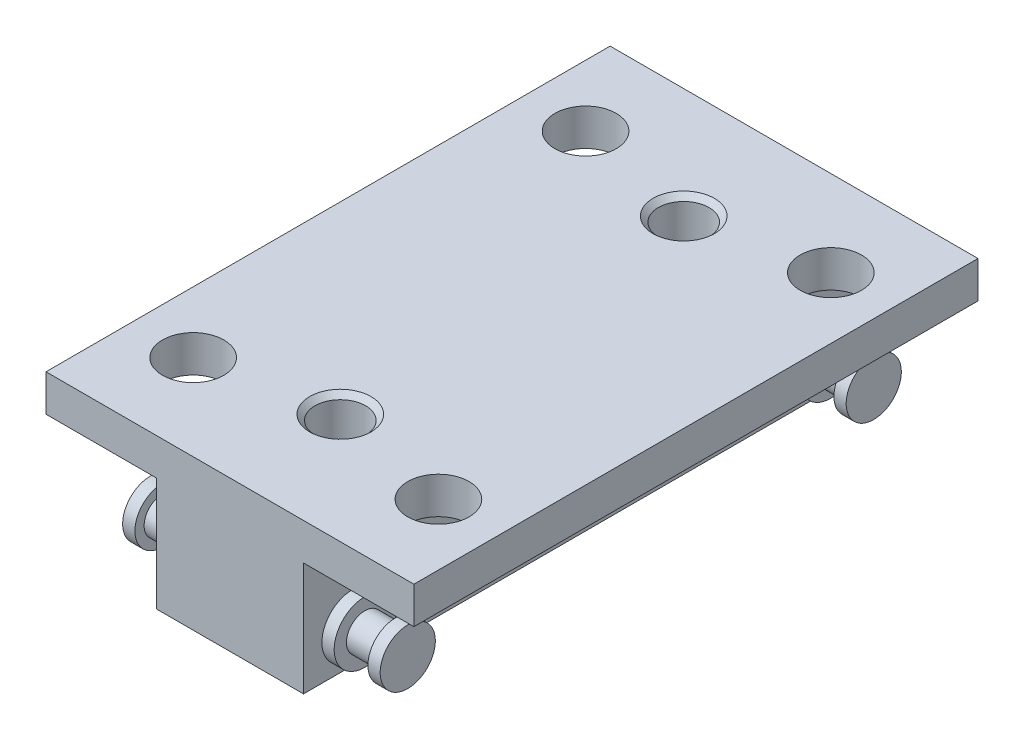
SolidWorks part; units mm, degrees
ref_plane "Front Plane" through (0, 0, 0) normal (0, 0, 1) x (1, 0, 0)
ref_plane "Top Plane" through (0, 0, 0) normal (0, 1, 0) x (1, 0, 0)
ref_plane "Right Plane" through (0, 0, 0) normal (1, 0, 0) x (0, 0, -1)
ref_plane "Plane1" through (0, 0, 0) normal (0, 0, 1) x (1, 0, 0)
sketch "Sketch1" plane through (0, 0, 0) normal (0, 0, 1) x (1, 0, 0)
  line L0 (-15, 6.25) -> (-15, 3.25)
  line L1 (-15, 3.25) -> (-6, 3.25)
  line L2 (-6, 3.25) -> (-6, -6)
  line L3 (-6, -6) -> (6, -6)
  line L4 (6, -6) -> (6, 3.25)
  line L5 (6, 3.25) -> (15, 3.25)
  line L6 (15, 3.25) -> (15, 6.25)
  line L7 (15, 6.25) -> (-15, 6.25)
extrude "Boss-Extrude1" add sketch "Sketch1" against normal blind 23 and the other way blind 23
ref_plane "Plane2" through (0, 0, 19) normal (0, 0, 1) x (1, 0, 0)
sketch "Sketch2" plane through (0, 0, 19) normal (0, 0, 1) x (1, 0, 0)
  line L0 (10.5, -3.125) -> (10.5, -5.375)
  line L1 (10.5, -5.375) -> (9.5, -5.375)
  line L2 (9.5, -5.375) -> (9.5, -4.625)
  line L3 (9.5, -4.625) -> (7, -4.625)
  line L4 (7, -4.625) -> (7, -5.625)
  line L5 (7, -5.625) -> (6, -5.625)
  line L6 (6, -5.625) -> (6, -4.625)
  line L7 (6, -4.625) -> (-6, -4.625)
  line L8 (-6, -4.625) -> (-6, -5.625)
  line L9 (-6, -5.625) -> (-7, -5.625)
  line L10 (-7, -5.625) -> (-7, -4.625)
  line L11 (-7, -4.625) -> (-9.5, -4.625)
  line L12 (-9.5, -4.625) -> (-9.5, -5.375)
  line L13 (-9.5, -5.375) -> (-10.5, -5.375)
  line L14 (-10.5, -5.375) -> (-10.5, -3.125)
  line L15 (-10.5, -3.125) -> (10.5, -3.125)
  line L16 (-10.5, -3.125) -> (10.5, -3.125) construction
revolve "Revolve1" add sketch "Sketch2" angle 360 about L16 reverse direction yes
ref_plane "Plane3" through (0, 0, -19) normal (0, 0, 1) x (1, 0, 0)
sketch "Sketch3" plane through (0, 0, -19) normal (0, 0, 1) x (1, 0, 0)
  line L0 (10.5, -3.125) -> (10.5, -5.375)
  line L1 (10.5, -5.375) -> (9.5, -5.375)
  line L2 (9.5, -5.375) -> (9.5, -4.625)
  line L3 (9.5, -4.625) -> (7, -4.625)
  line L4 (7, -4.625) -> (7, -5.625)
  line L5 (7, -5.625) -> (6, -5.625)
  line L6 (6, -5.625) -> (6, -4.625)
  line L7 (6, -4.625) -> (-6, -4.625)
  line L8 (-6, -4.625) -> (-6, -5.625)
  line L9 (-6, -5.625) -> (-7, -5.625)
  line L10 (-7, -5.625) -> (-7, -4.625)
  line L11 (-7, -4.625) -> (-9.5, -4.625)
  line L12 (-9.5, -4.625) -> (-9.5, -5.375)
  line L13 (-9.5, -5.375) -> (-10.5, -5.375)
  line L14 (-10.5, -5.375) -> (-10.5, -3.125)
  line L15 (-10.5, -3.125) -> (10.5, -3.125)
  line L16 (-10.5, -3.125) -> (10.5, -3.125) construction
revolve "Revolve2" add sketch "Sketch3" angle 360 about L16 reverse direction yes
ref_plane "Plane4" through (0, 0, 0) normal (1, 0, 0) x (0, 0, -1)
sketch "Sketch4" plane through (0, 0, 0) normal (1, 0, 0) x (0, 0, -1)
  line L0 (-14, 6.25) -> (-11.5, 6.25)
  line L1 (-11.5, 6.25) -> (-11.933, 5.817)
  line L2 (-11.933, 5.817) -> (-11.933, -5.567)
  line L3 (-11.933, -5.567) -> (-11.5, -6)
  line L4 (-11.5, -6) -> (-14, -6)
  line L5 (-14, -6) -> (-14, 6.25)
  line L6 (-14, -6) -> (-14, 6.25) construction
revolve "Cut-Revolve1" cut sketch "Sketch4" angle 360 about L6 reverse direction yes
ref_plane "Plane5" through (0, 0, 0) normal (1, 0, 0) x (0, 0, -1)
sketch "Sketch5" plane through (0, 0, 0) normal (1, 0, 0) x (0, 0, -1)
  line L0 (14, 6.25) -> (16.5, 6.25)
  line L1 (16.5, 6.25) -> (16.067, 5.817)
  line L2 (16.067, 5.817) -> (16.067, -5.567)
  line L3 (16.067, -5.567) -> (16.5, -6)
  line L4 (16.5, -6) -> (14, -6)
  line L5 (14, -6) -> (14, 6.25)
  line L6 (14, -6) -> (14, 6.25) construction
revolve "Cut-Revolve2" cut sketch "Sketch5" angle 360 about L6 reverse direction yes
sketch "Sketch6" plane through (0, 6.25, 0) normal (0, 1, 0) x (1, 0, 0)
  line L0 (15, 23) -> (-15, 23) construction
  line L1 (-15, -23) -> (-15, 23) construction
  line L2 (15, -23) -> (15, 23) construction
  line L3 (15, -23) -> (-15, -23) construction
  circle A0 centre (-10, 16) radius 2.5
  circle A1 centre (10, 16) radius 2.5
  circle A2 centre (-10, -16) radius 2.5
  circle A3 centre (10, -16) radius 2.5
  dimension "D1" = 5
  dimension "D2" = 7
  dimension "D3" = 5
  dimension "D5" = 5
  dimension "D7" = 7
  dimension "D4" = 2
  dimension "D6" = 2
extrude "Cut-Extrude1" cut sketch "Sketch6" against normal up to surface (3 mm away)
